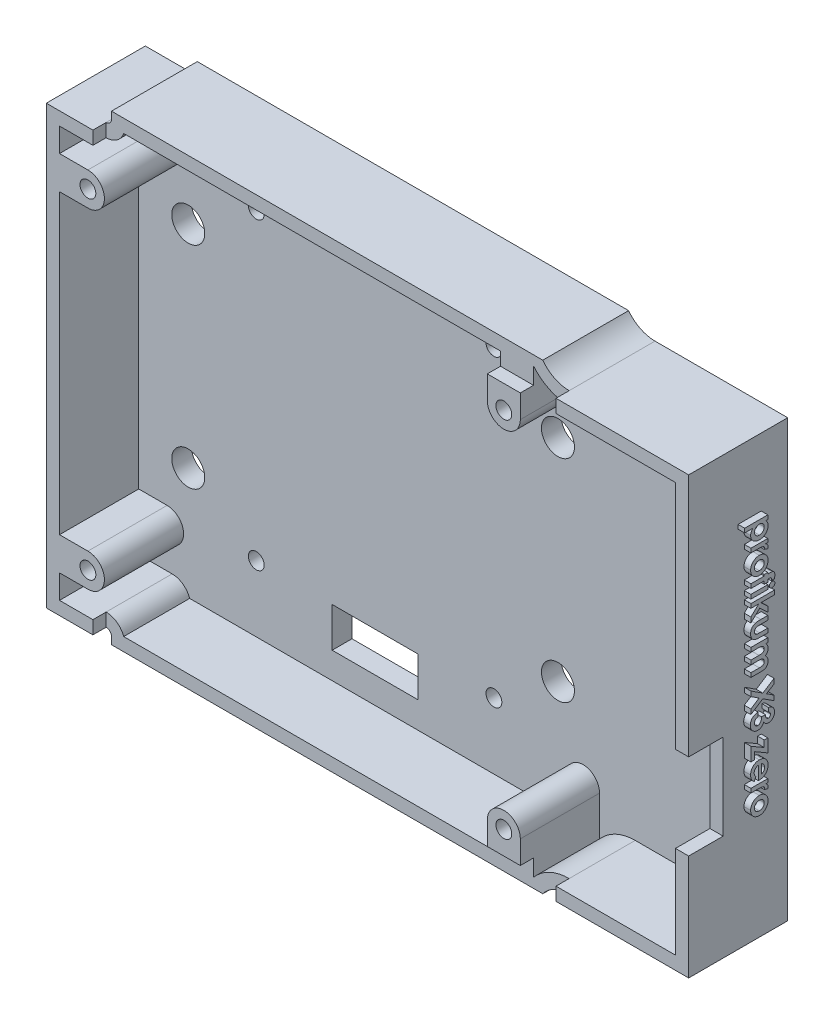
SolidWorks part; units mm, degrees
ref_plane "Ebene vorne" through (0, 0, 0) normal (0, 0, 1) x (1, 0, 0)
ref_plane "Ebene oben" through (0, 0, 0) normal (0, 1, 0) x (1, 0, 0)
ref_plane "Ebene rechts" through (0, 0, 0) normal (1, 0, 0) x (0, 0, -1)
sketch "Skizze1" plane through (0, 0, 0) normal (0, 0, 1) x (1, 0, 0)
  line L0 (-40.78, 38.7) -> (-40.78, 33.92)
  line L1 (-41.59, 33.11) -> (-48.65, 33.11)
  line L2 (-48.65, 33.11) -> (-48.65, -33.11)
  line L3 (-48.65, -33.11) -> (-41.59, -33.11)
  line L4 (-40.78, -33.92) -> (-40.78, -38.7)
  line L5 (-40.78, -38.7) -> (-39.35, -38.7)
  line L6 (-39.35, -38.7) -> (-39.35, 38.7)
  line L7 (-39.35, 38.7) -> (-40.78, 38.7)
  line L8 (48.65, 3) -> (45.65, 3)
  line L9 (45.65, 3) -> (45.65, -30)
  line L10 (45.65, -30) -> (34.2, -30)
  line L11 (34.2, -33) -> (48.65, -33)
  line L12 (48.65, -33) -> (48.65, 3)
  line L13 (45.65, 18) -> (48.65, 18)
  line L14 (48.65, 18) -> (48.65, 33)
  line L15 (48.65, 33) -> (34.2, 33)
  line L16 (34.2, 30) -> (45.65, 30)
  line L17 (45.65, 30) -> (45.65, 18)
  line L18 (34.2, 33) -> (28.5521, 33)
  line L19 (23.85, 36.3) -> (5.65, 36.3)
  line L20 (2.287, 35) -> (-20.522, 35)
  line L21 (-25.35, 38.7) -> (-27.35, 38.7)
  line L22 (-27.35, 38.7) -> (-27.35, -38.7)
  line L23 (-27.35, -38.7) -> (-25.35, -38.7)
  line L24 (-20.522, -35) -> (2.287, -35)
  line L25 (5.65, -36.3) -> (23.85, -36.3)
  line L26 (28.5521, -33) -> (34.2, -33)
  line L27 (34.2, -30) -> (23.85, -30)
  line L28 (23.85, -30) -> (23.85, -24)
  line L29 (23.85, -24) -> (17.45, -24)
  line L30 (17.45, -24) -> (17.45, -33.3)
  line L31 (17.45, -33.3) -> (9.3559, -33.3)
  line L32 (7.65, -33) -> (-24.35, -33)
  line L33 (-24.35, -33) -> (-24.35, 33)
  line L34 (-24.35, 33) -> (7.65, 33)
  line L35 (9.3559, 33.3) -> (17.45, 33.3)
  line L36 (17.45, 33.3) -> (17.45, 24)
  line L37 (17.45, 24) -> (23.85, 24)
  line L38 (23.85, 24) -> (23.85, 30)
  line L39 (23.85, 30) -> (34.2, 30)
  line L40 (-39.35, -38.7) -> (-27.35, -38.7)
  line L41 (-39.35, 38.7) -> (-27.35, 38.7)
  line L42 (48.65, 18) -> (48.65, 3)
  arc A0 (-41.59, 33.11) -> (-40.78, 33.92) centre (-41.59, 33.92) ccw
  arc A1 (-40.78, -33.92) -> (-41.59, -33.11) centre (-41.59, -33.92) ccw
  arc A2 (23.85, 36.3) -> (28.5521, 33) centre (28.5521, 38) ccw
  arc A3 (2.287, 35) -> (5.65, 36.3) centre (2.287, 40) ccw
  arc A4 (-25.35, 38.7) -> (-20.522, 35) centre (-20.522, 40) ccw
  arc A5 (-20.522, -35) -> (-25.35, -38.7) centre (-20.522, -40) ccw
  arc A6 (5.65, -36.3) -> (2.287, -35) centre (2.287, -40) ccw
  arc A7 (28.5521, -33) -> (23.85, -36.3) centre (28.5521, -38) ccw
  arc A8 (7.65, -33) -> (9.3559, -33.3) centre (9.3559, -28.3) ccw
  arc A9 (9.3559, 33.3) -> (7.65, 33) centre (9.3559, 28.3) ccw
extrude "Aufsatz-Linear austragen1" add sketch "Skizze1" along normal blind 15 contours A1 L4 L5 L6 L7 L0 A0 L1 L2 L3 | L41 L6 L40 L22 | A9 L35 L36 L37 L38 L39 L16 L17 L13 L14 L15 L18 A2 L19 A3 L20 A4 L21 L22 L23 A5 L24 A6 L25 A7 L26 L11 L12 L8 L9 L10 L27 L28 L29 L30 L31 A8 L32 L33 L34 | L35 A9 L34 L33 L32 A8 L31 L30 L29 L28 L27 L10 L9 L8 L42 L13 L17 L16 L39 L38 L37 L36 region at (-43.8991, 0, 0) region at (-33.35, 0, 0) region at (-26.35, 37.6153, 0) region at (10.0511, 0.1068, 0)
sketch "Skizze7" plane through (0, 0, 0) normal (0, 0, -1) x (-1, 0, 0)
  line L1 (17.35, -29) -> (4.35, -29)
  line L2 (17.35, -29) -> (17.35, -23)
  line L3 (17.35, -23) -> (4.35, -23)
  line L4 (4.35, -29) -> (4.35, -23)
  line L5 (17.35, 23) -> (4.35, 23)
  line L6 (17.35, 23) -> (17.35, 29)
  line L7 (17.35, 29) -> (4.35, 29)
  line L8 (4.35, 23) -> (4.35, 29)
extrude "Schnitt-Linear austragen6" cut sketch "Skizze7" against normal through all both
sketch "Skizze2" plane through (0, 0, 15) normal (0, 0, 1) x (1, 0, 0)
  line L56 (46.65, -31) -> (46.65, 31)
  line L57 (46.65, 31) -> (28.5521, 31)
  line L58 (22.6099, 34.3) -> (6.3502, 34.3)
  line L59 (2.287, 33) -> (-20.522, 33)
  line L60 (-26.6953, 36.7) -> (-38.78, 36.7)
  line L61 (-38.78, 36.7) -> (-38.78, 33.92)
  line L62 (-41.59, 31.11) -> (-46.65, 31.11)
  line L63 (-46.65, 31.11) -> (-46.65, -31.11)
  line L64 (-46.65, -31.11) -> (-41.59, -31.11)
  line L65 (-38.78, -33.92) -> (-38.78, -36.7)
  line L66 (-38.78, -36.7) -> (-26.6953, -36.7)
  line L67 (-20.522, -33) -> (2.287, -33)
  line L68 (6.3502, -34.3) -> (22.6099, -34.3)
  line L69 (28.5521, -31) -> (46.65, -31)
  line L70 (46.65, -31) -> (46.65, 31)
  line L71 (46.65, 31) -> (28.5521, 31)
  line L72 (22.6099, 34.3) -> (6.3502, 34.3)
  line L73 (2.287, 33) -> (-20.522, 33)
  line L74 (-26.6953, 36.7) -> (-38.78, 36.7)
  line L75 (-38.78, 36.7) -> (-38.78, 33.92)
  line L76 (-41.59, 31.11) -> (-46.65, 31.11)
  line L77 (-46.65, 31.11) -> (-46.65, -31.11)
  line L78 (-46.65, -31.11) -> (-41.59, -31.11)
  line L79 (-38.78, -33.92) -> (-38.78, -36.7)
  line L80 (-38.78, -36.7) -> (-26.6953, -36.7)
  line L81 (-20.522, -33) -> (2.287, -33)
  line L82 (6.3502, -34.3) -> (22.6099, -34.3)
  line L83 (28.5521, -31) -> (46.65, -31)
  arc A32 (22.6099, 34.3) -> (28.5521, 31) centre (28.5521, 38) ccw
  arc A33 (2.287, 33) -> (6.3502, 34.3) centre (2.287, 40) ccw
  arc A34 (-26.6953, 36.7) -> (-20.522, 33) centre (-20.522, 40) ccw
  arc A35 (-41.59, 31.11) -> (-38.78, 33.92) centre (-41.59, 33.92) ccw
  arc A36 (-38.78, -33.92) -> (-41.59, -31.11) centre (-41.59, -33.92) ccw
  arc A37 (-20.522, -33) -> (-26.6953, -36.7) centre (-20.522, -40) ccw
  arc A38 (6.3502, -34.3) -> (2.287, -33) centre (2.287, -40) ccw
  arc A39 (28.5521, -31) -> (22.6099, -34.3) centre (28.5521, -38) ccw
  arc A40 (22.6099, 34.3) -> (28.5521, 31) centre (28.5521, 38) ccw
  arc A41 (2.287, 33) -> (6.3502, 34.3) centre (2.287, 40) ccw
  arc A42 (-26.6953, 36.7) -> (-20.522, 33) centre (-20.522, 40) ccw
  arc A43 (-41.59, 31.11) -> (-38.78, 33.92) centre (-41.59, 33.92) ccw
  arc A44 (-38.78, -33.92) -> (-41.59, -31.11) centre (-41.59, -33.92) ccw
  arc A45 (-20.522, -33) -> (-26.6953, -36.7) centre (-20.522, -40) ccw
  arc A46 (6.3502, -34.3) -> (2.287, -33) centre (2.287, -40) ccw
  arc A47 (28.5521, -31) -> (22.6099, -34.3) centre (28.5521, -38) ccw
  dimension "D1" = 2
extrude "Schnitt-Linear austragen1" cut sketch "Skizze2" against normal blind 12
sketch "Skizze3" plane through (0, 0, 3) normal (0, 0, 1) x (1, 0, 0)
  line L0 (-48.65, 0) -> (48.65, 0) construction
  line L1 (-48.65, 0) -> (48.65, 0) construction
  line L2 (48.65, -33) -> (48.65, 33) construction
  line L3 (-48.65, 33.11) -> (-48.65, -33.11) construction
  circle A5 centre (-42.35, 25) radius 1.2
  circle A6 centre (20.65, 27.5) radius 1.2
  circle A7 centre (20.65, -27.5) radius 1.2
  circle A8 centre (-42.35, -25) radius 1.2
  dimension "D1" = 2.4
  dimension "D2" = 2.4
extrude "Schnitt-Linear austragen2" cut sketch "Skizze3" against normal blind 10
sketch "Skizze4" plane through (48.65, 0, 0) normal (1, 0, 0) x (0, 0, -1)
  line L0 (-15, -33) -> (-15, 33) construction
  line L1 (-15, -4) -> (-9.78, -4)
  line L2 (-15, -4) -> (-15, -17)
  line L3 (-15, -17) -> (-9.78, -17)
  line L4 (-9.78, -4) -> (-9.78, -17)
  line L5 (-15, -4) -> (-19.215, -4) construction
  point P9 (-12.39, -17)
  dimension "D1" = 5.22
  dimension "D2" = 13
extrude "Schnitt-Linear austragen3" cut sketch "Skizze4" against normal blind 5
sketch "Skizze5" plane through (0, 0, 0) normal (0, 0, -1) x (-1, 0, 0)
  circle A4 centre (-7.15, 23) radius 1.2
  circle A5 centre (28.85, 23) radius 1.2
  circle A6 centre (-7.15, -23) radius 1.2
  circle A7 centre (28.85, -23) radius 1.2
extrude "Schnitt-Linear austragen4" cut sketch "Skizze5" against normal through all both
sketch "Skizze6" plane through (0, 0, 0) normal (0, 0, -1) x (-1, 0, 0)
  line L0 (11.15, -17.75) -> (11.15, 17.75) construction
  line L1 (-21.35, -17.75) -> (43.65, -17.75) construction
  line L2 (43.65, 17.75) -> (-21.35, 17.75) construction
  line L3 (48.65, 0) -> (-26.35, 0) construction
  line L4 (48.65, 33.11) -> (48.65, -33.11) construction
  line L5 (-26.35, -10) -> (-26.35, 10) construction
  circle A0 centre (-16.85, -16) radius 2.5
  circle A1 centre (-16.85, 16) radius 2.5
  circle A2 centre (39.15, 16) radius 2.5
  circle A3 centre (39.15, -16) radius 2.5
  dimension "D1" = 5
  dimension "D2" = 28
  dimension "D3" = 16
extrude "Schnitt-Linear austragen5" cut sketch "Skizze6" against normal through all both
sketch "Skizze8" plane through (0, 0, 3) normal (0, 0, 1) x (1, 0, 0)
  line L0 (-48.65, 0) -> (48.65, 0) construction
  line L1 (-48.65, 33.11) -> (-48.65, -33.11) construction
  line L2 (48.65, -4) -> (48.65, 33) construction
  line L3 (0, 0) -> (0, 35) construction
  line L4 (2.287, 35) -> (-20.522, 35) construction
  circle A0 centre (-42.35, 25) radius 2.5
  circle A1 centre (-42.35, 25) radius 1.2
  circle A2 centre (-42.35, -25) radius 1.2
  circle A3 centre (-42.35, -25) radius 2.5
  circle A4 centre (20.65, 27.5) radius 2.5
  circle A5 centre (20.65, 27.5) radius 1.2
  circle A6 centre (20.65, -27.5) radius 1.2
  circle A7 centre (20.65, -27.5) radius 2.5
  dimension "D1" = 5
  dimension "D2" = 5
extrude "Aufsatz-Linear austragen2" add sketch "Skizze8" along normal up to surface (12 mm away) up to face at (-5.0444, -0.875, 15)
sketch "Skizze9" plane through (0, 0, 3) normal (0, 0, 1) x (1, 0, 0)
  line L0 (20.6578, 29.8022) -> (20.6578, 36.7352)
  line L1 (20.6578, 36.7352) -> (-46.65, 36.7352)
  line L2 (-46.65, 36.7352) -> (-46.65, 27.3022)
  line L3 (-46.65, 31.11) -> (-46.65, -31.11) construction
  line L4 (-46.65, 27.3022) -> (18.1578, 27.3022)
  line L5 (-48.65, 0) -> (46.65, 0) construction
  line L6 (-48.65, 33.11) -> (-48.65, -33.11) construction
  line L7 (46.65, -31) -> (46.65, 31) construction
  line L9 (18.15, 33) -> (18.15, 27.5)
  line L17 (-46.65, -27.3022) -> (18.1578, -27.3022)
  line L18 (-46.65, -36.7352) -> (-46.65, -27.3022)
  line L19 (20.6578, -36.7352) -> (-46.65, -36.7352)
  line L20 (20.6578, -29.8022) -> (20.6578, -36.7352)
  line L21 (-20.522, -33) -> (-38.9349, -33)
  line L22 (-20.522, -35) -> (-38.78, -35)
  line L23 (-38.78, -33.92) -> (-38.78, -36.7) construction
  line L24 (-38.78, -35) -> (-38.9349, -33)
  line L25 (-20.522, -33) -> (-20.522, -35)
  line L26 (-20.522, 33) -> (-20.522, 35)
  line L27 (-38.78, 35) -> (-38.9349, 33)
  line L28 (-20.522, 35) -> (-38.78, 35)
  line L29 (-20.522, 33) -> (-38.9349, 33)
  line L30 (2.287, 33) -> (18.15, 33)
  line L31 (2.287, 35) -> (24.5521, 35)
  line L32 (24.5521, 35) -> (24.5521, 34.3)
  line L33 (23.15, 34.3) -> (24.5521, 34.3)
  line L34 (2.287, 35) -> (2.287, 33)
  line L35 (2.287, -35) -> (2.287, -33)
  line L36 (23.15, -34.3) -> (24.5521, -34.3)
  line L37 (24.5521, -35) -> (24.5521, -34.3)
  line L38 (2.287, -35) -> (24.5521, -35)
  line L39 (2.287, -33) -> (18.15, -33)
  line L40 (23.15, -27.5) -> (23.15, -34.3)
  line L41 (18.15, -27.5) -> (18.15, -33)
  line L42 (23.15, 34.3) -> (23.15, 27.5)
  circle A0 centre (20.65, 27.5) radius 2.5 construction
  circle A1 centre (20.65, 27.5) radius 2.5 construction
  arc A2 (20.6578, 29.8022) -> (18.1578, 27.3022) centre (18.1578, 29.8022) cw
  circle A3 centre (18.1578, 29.8022) radius 1.2
  arc A6 (18.15, 27.5) -> (23.15, 27.5) centre (20.65, 27.5) ccw
  circle A11 centre (18.1578, -29.8022) radius 1.2
  arc A12 (20.6578, -29.8022) -> (18.1578, -27.3022) centre (18.1578, -29.8022) ccw
  arc A13 (-38.78, -33.92) -> (-41.59, -31.11) centre (-41.59, -33.92) ccw construction
  arc A14 (23.85, 36.3) -> (28.5521, 33) centre (28.5521, 38) ccw construction
  circle A15 centre (20.65, -27.5) radius 1.2
  arc A16 (23.15, -27.5) -> (18.15, -27.5) centre (20.65, -27.5) ccw
  circle M1 centre (20.65, 27.5) radius 2.5
  arc M22 (28.5521, 31) -> (22.6099, 34.3) centre (28.5521, 38) cw
  line M23 (22.6099, 34.3) -> (6.3502, 34.3)
  arc M24 (6.3502, 34.3) -> (2.287, 33) centre (2.287, 40) cw
  arc M38 (2.287, -33) -> (6.3502, -34.3) centre (2.287, -40) cw
  line M39 (6.3502, -34.3) -> (22.6099, -34.3)
  arc M40 (22.6099, -34.3) -> (28.5521, -31) centre (28.5521, -38) cw
  circle M42 centre (20.65, -27.5) radius 2.5
  dimension "D1" = 2.5
extrude "Aufsatz-Linear austragen3" add sketch "Skizze9" along normal up to surface (12 mm away) contours L40 L20 M42 M39 M40 | A11 L41 M42 | L42 L0 M22 M23 M1 | A3 L0 L30 L9 M1 M23 M24 | L9 A3 M1 | A3 L9 M1 | A11 L41 L39 L20 M42 M38 M39 | L41 A11 M42 region at (14.4987, 33.1222, 3) region at (21.9627, 31.8094, 3) region at (18.6267, 29.9018, 3) region at (18.2291, 28.3365, 3) region at (21.9627, -31.8094, 3) region at (18.2291, -28.3365, 3) region at (14.4987, -33.1222, 3) region at (18.6267, -29.9018, 3) up to face at (-5.0444, -0.875, 15)
sketch "Skizze10" plane through (0, 0, 15) normal (0, 0, 1) x (1, 0, 0)
  line L0 (-40.78, 38.7) -> (-40.78, 33.92) construction
  line L1 (-40.78, 35) -> (36.193, 35)
  line L2 (-40.78, 35) -> (-40.78, 40.1609)
  line L3 (-40.78, 40.1609) -> (36.193, 40.1609)
  line L4 (36.193, 35) -> (36.193, 40.1609)
  line L5 (-48.65, 0) -> (46.65, 0) construction
  line L6 (-48.65, 33.11) -> (-48.65, -33.11) construction
  line L7 (46.65, -31) -> (46.65, 31) construction
  line L8 (36.193, -35) -> (36.193, -40.1609)
  line L9 (-40.78, -40.1609) -> (36.193, -40.1609)
  line L10 (-40.78, -35) -> (-40.78, -40.1609)
  line L11 (-40.78, -35) -> (36.193, -35)
extrude "Schnitt-Linear austragen7" cut sketch "Skizze10" against normal through all both and the other way through all
sketch "Skizze11" plane through (0, 0, 15) normal (0, 0, 1) x (1, 0, 0)
  line L19 (-48.65, 0) -> (0, 0) construction
  line L20 (-48.65, 33.11) -> (-48.65, -33.11) construction
  line L33 (-41.59, 31.11) -> (-41.59, 35)
  line L34 (-41.59, 35) -> (28.5521, 35)
  line L35 (28.5521, 35) -> (28.5521, 31)
  line L36 (28.5521, 31) -> (18.15, 31)
  line L38 (18.15, 31) -> (18.15, 33)
  line L39 (18.15, 33) -> (-38.9349, 33)
  line L40 (-38.9349, 33) -> (-38.9349, 31.11)
  line L41 (-38.9349, 31.11) -> (-41.59, 31.11)
  line L42 (-38.9349, -33) -> (-38.9349, -31.11)
  line L43 (18.15, -33) -> (-38.9349, -33)
  line L44 (18.15, -31) -> (18.15, -33)
  line L45 (28.5521, -31) -> (18.15, -31)
  line L46 (28.5521, -35) -> (28.5521, -31)
  line L47 (-41.59, -35) -> (28.5521, -35)
  line L48 (-41.59, -31.11) -> (-41.59, -35)
  line L49 (-38.9349, -31.11) -> (-41.59, -31.11)
extrude "Schnitt-Linear austragen8" cut sketch "Skizze11" against normal blind 2
sketch "Skizze12" plane through (0, 0, 3) normal (0, 0, 1) x (1, 0, 0)
  line L0 (-56.6131, 0) -> (54.1226, 0) construction
  line L1 (-20.522, -35) -> (-20.522, -33)
  line L2 (-40.78, 35) -> (-20.522, 35)
  line L3 (-40.78, 35) -> (-40.78, 33)
  line L4 (-40.78, 33) -> (-20.522, 33)
  line L5 (-20.522, 35) -> (-20.522, 33)
  line L6 (-40.78, -33) -> (-20.522, -33)
  line L7 (-40.78, -35) -> (-40.78, -33)
  line L8 (-40.78, -35) -> (-20.522, -35)
extrude "Aufsatz-Linear austragen4" add sketch "Skizze12" along normal up to surface (10 mm away) up to face at (13.0662, 32.6656, 13)
sketch "Skizze13" plane through (0, 0, 3) normal (0, 0, 1) x (1, 0, 0)
  line L0 (-42.35, 27.5) -> (-46.65, 27.5)
  line L1 (-46.65, 31.11) -> (-46.65, -31.11) construction
  line L2 (-42.35, 22.5) -> (-46.65, 22.5)
  line L3 (-46.65, 22.5) -> (-46.65, 27.5)
  line L4 (-70.2115, 0) -> (90.3096, 0) construction
  line L5 (-46.65, -22.5) -> (-46.65, -27.5)
  line L6 (-42.35, -22.5) -> (-46.65, -22.5)
  line L7 (-42.35, -27.5) -> (-46.65, -27.5)
  circle A0 centre (-42.35, 25) radius 2.5 construction
  circle A1 centre (-42.35, 25) radius 2.5 construction
  arc A2 (-42.35, 27.5) -> (-42.35, 22.5) centre (-42.35, 25) ccw
  arc A3 (-42.35, -27.5) -> (-42.35, -22.5) centre (-42.35, -25) cw
extrude "Aufsatz-Linear austragen5" add sketch "Skizze13" along normal up to surface (12 mm away) up to face at (-41.15, 25, 15)
sketch "Skizze17" plane through (48.65, 0, 0) normal (1, 0, 0) x (0, 0, -1)
  line L0 (-4.0129, 22.1349) -> (-4.3011, 22.1349)
  line L1 (-6.2818, 22.1349) -> (-7.5129, 22.1349)
  line L2 (-7.5129, 22.1349) -> (-7.5129, 22.7631)
  line L3 (-7.5129, 22.7631) -> (-4.0129, 22.7631)
  line L4 (-4.0129, 22.7631) -> (-4.0129, 22.1349)
  line L5 (-4.0129, 19.6669) -> (-4.0129, 19.1284)
  line L6 (-4.0129, 19.1284) -> (-4.3277, 19.1284)
  line L7 (-4.0312, 18.3208) -> (-4.5633, 18.5157)
  line L8 (-5.4103, 19.0408) -> (-5.5351, 19.0387)
  line L9 (-5.5351, 19.0387) -> (-6.5706, 19.0387)
  line L10 (-6.5706, 19.0387) -> (-6.5706, 19.6669)
  line L11 (-6.5706, 19.6669) -> (-4.0129, 19.6669)
  line L12 (-4.0129, 15.2246) -> (-4.0129, 15.0002)
  line L13 (-3.0279, 13.8784) -> (-3.5165, 13.8784)
  line L14 (-3.6771, 14.3272) -> (-4.0129, 14.3293)
  line L15 (-4.0129, 14.3293) -> (-4.0129, 13.9233)
  line L16 (-4.0129, 13.9233) -> (-4.5514, 13.9233)
  line L17 (-4.5514, 13.9233) -> (-4.5514, 14.372)
  line L18 (-4.5514, 14.372) -> (-6.5706, 14.372)
  line L19 (-6.5706, 14.372) -> (-6.5706, 15.0002)
  line L20 (-6.5706, 15.0002) -> (-4.5514, 15.0002)
  line L21 (-4.5514, 15.0002) -> (-4.5514, 15.2246)
  line L22 (-4.5514, 15.2246) -> (-4.0129, 15.2246)
  line L23 (-4.0129, 13.6092) -> (-4.0129, 12.981)
  line L24 (-4.0129, 12.981) -> (-6.5706, 12.981)
  line L25 (-6.5706, 12.981) -> (-6.5706, 13.6092)
  line L26 (-6.5706, 13.6092) -> (-4.0129, 13.6092)
  line L27 (-2.9809, 12.3977) -> (-2.9809, 11.7695)
  line L28 (-2.9809, 11.7695) -> (-5.0744, 11.7695)
  line L29 (-5.0744, 11.7695) -> (-4.0129, 10.7921)
  line L30 (-4.0129, 10.7921) -> (-4.0129, 10.016)
  line L31 (-4.0129, 10.016) -> (-5.2322, 11.1385)
  line L32 (-5.2322, 11.1385) -> (-6.5706, 9.8554)
  line L33 (-6.5706, 9.8554) -> (-6.5706, 10.6463)
  line L34 (-6.5706, 10.6463) -> (-5.399, 11.7695)
  line L35 (-5.399, 11.7695) -> (-6.5706, 11.7695)
  line L36 (-6.5706, 11.7695) -> (-6.5706, 12.3977)
  line L37 (-6.5706, 12.3977) -> (-2.9809, 12.3977)
  line L38 (-4.0129, 9.5708) -> (-4.0129, 8.9425)
  line L39 (-4.0129, 8.9425) -> (-5.2406, 8.9425)
  line L40 (-5.2616, 7.9105) -> (-4.0129, 7.9105)
  line L41 (-4.0129, 7.9105) -> (-4.0129, 7.2823)
  line L42 (-4.0129, 7.2823) -> (-5.0877, 7.2823)
  line L43 (-5.0695, 9.5708) -> (-4.0129, 9.5708)
  line L44 (-4.0129, 6.6541) -> (-4.0129, 6.0259)
  line L45 (-4.0129, 6.0259) -> (-4.3186, 6.0259)
  line L46 (-5.0828, 2.7054) -> (-6.5706, 2.7054)
  line L47 (-6.5706, 2.7054) -> (-6.5706, 3.3336)
  line L48 (-6.5706, 3.3336) -> (-5.2862, 3.3336)
  line L49 (-5.4285, 4.3656) -> (-6.5706, 4.3656)
  line L50 (-6.5706, 4.3656) -> (-6.5706, 4.9938)
  line L51 (-6.5706, 4.9938) -> (-5.3444, 4.9938)
  line L52 (-5.4446, 6.0259) -> (-6.5706, 6.0259)
  line L53 (-6.5706, 6.0259) -> (-6.5706, 6.6541)
  line L54 (-6.5706, 6.6541) -> (-4.0129, 6.6541)
  line L55 (-3.0706, 0.8551) -> (-3.0706, 0.1147)
  line L56 (-3.0706, 0.1147) -> (-4.1945, -0.6165)
  line L57 (-4.1945, -0.6165) -> (-3.0706, -1.3492)
  line L58 (-3.0706, -1.3492) -> (-3.0706, -2.0903)
  line L59 (-3.0706, -2.0903) -> (-4.7631, -0.9867)
  line L60 (-4.7631, -0.9867) -> (-6.5706, -2.1632)
  line L61 (-6.5706, -2.1632) -> (-6.5706, -1.4228)
  line L62 (-6.5706, -1.4228) -> (-5.331, -0.6165)
  line L63 (-5.331, -0.6165) -> (-6.5706, 0.1918)
  line L64 (-6.5706, 0.1918) -> (-6.5706, 0.9329)
  line L65 (-6.5706, 0.9329) -> (-4.7624, -0.2464)
  line L66 (-4.7624, -0.2464) -> (-3.0706, 0.8551)
  line L67 (-3.9232, -3.1728) -> (-3.9232, -2.5446)
  line L68 (-5.4937, -2.3651) -> (-5.4937, -2.9933)
  line L69 (-4.9552, -3.2626) -> (-4.3719, -3.2626)
  line L70 (-4.0129, -6.4933) -> (-4.0129, -8.4677)
  line L71 (-4.0129, -8.4677) -> (-6.0322, -7.2912)
  line L72 (-6.0322, -7.2912) -> (-6.0322, -8.378)
  line L73 (-6.0322, -8.378) -> (-6.5706, -8.378)
  line L74 (-6.5706, -8.378) -> (-6.5706, -6.3139)
  line L75 (-6.5706, -6.3139) -> (-4.5514, -7.4903)
  line L76 (-4.5514, -7.4903) -> (-4.5514, -6.4933)
  line L77 (-4.5514, -6.4933) -> (-4.0129, -6.4933)
  line L78 (-5.4488, -11.3823) -> (-5.4488, -9.3651)
  line L79 (-5.8113, -10.679) -> (-6.0616, -11.2049)
  line L80 (-5.3303, -11.3844) -> (-5.4488, -11.3823)
  line L81 (-4.9552, -9.41) -> (-4.9552, -10.7562)
  line L82 (-4.0129, -11.8331) -> (-4.0129, -12.3716)
  line L83 (-4.0129, -12.3716) -> (-4.3277, -12.3716)
  line L84 (-4.0312, -13.1792) -> (-4.5633, -12.9843)
  line L85 (-5.4103, -12.4592) -> (-5.5351, -12.4613)
  line L86 (-5.5351, -12.4613) -> (-6.5706, -12.4613)
  line L87 (-6.5706, -12.4613) -> (-6.5706, -11.8331)
  line L88 (-6.5706, -11.8331) -> (-4.0129, -11.8331)
  spline S0 degree 3 poles (-4.3011, 22.1349) (-4.2469, 22.0791) (-4.1746, 21.9887) (-4.0965, 21.8582) (-4.0499, 21.7575) (-4.0133, 21.6538) (-3.9784, 21.5093) (-3.9672, 21.3976) (-3.9681, 21.3223) knots 0 0 0 0 0.258836 0.383778 0.505657 0.627755 0.749517 1 1 1 1
  spline S1 degree 3 poles (-3.9681, 21.3223) (-3.9678, 21.2412) (-3.9787, 21.1205) (-4.0185, 20.9661) (-4.0594, 20.8562) (-4.1126, 20.7515) (-4.1763, 20.6507) (-4.253, 20.5556) (-4.34, 20.4661) (-4.4354, 20.3833) (-4.539, 20.3114) (-4.6496, 20.2514) (-4.7658, 20.2006) (-4.8896, 20.1635) (-5.0658, 20.1245) (-5.2037, 20.1165) (-5.2967, 20.1156) knots 0 0 0 0 0.12138 0.180256 0.238142 0.296489 0.355776 0.416247 0.479076 0.54232 0.604902 0.667516 0.730346 0.794405 0.860608 1 1 1 1
  spline S2 degree 3 poles (-5.2967, 20.1156) (-5.387, 20.1159) (-5.5208, 20.1254) (-5.6924, 20.1645) (-5.8133, 20.2048) (-5.9287, 20.2561) (-6.0384, 20.3187) (-6.1423, 20.3929) (-6.2387, 20.4778) (-6.3261, 20.5705) (-6.4044, 20.6672) (-6.4686, 20.7696) (-6.5229, 20.8753) (-6.5643, 20.9859) (-6.6037, 21.1404) (-6.6166, 21.2604) (-6.6155, 21.3412) knots 0 0 0 0 0.135343 0.199959 0.263049 0.325881 0.388744 0.451973 0.516706 0.580831 0.6426 0.702706 0.761562 0.820266 0.879182 1 1 1 1
  spline S3 degree 3 poles (-6.6155, 21.3412) (-6.6159, 21.4132) (-6.6056, 21.5198) (-6.574, 21.6576) (-6.5391, 21.7563) (-6.4927, 21.8527) (-6.4133, 21.9843) (-6.3371, 22.0756) (-6.2818, 22.1349) knots 0 0 0 0 0.243991 0.362118 0.479017 0.598573 0.724533 1 1 1 1
  spline S4 degree 3 poles (-4.5514, 21.4583) (-4.5524, 21.5081) (-4.5566, 21.5823) (-4.5791, 21.6767) (-4.6006, 21.7434) (-4.6296, 21.8065) (-4.6647, 21.8665) (-4.7066, 21.9228) (-4.7536, 21.9758) (-4.8065, 22.0234) (-4.8631, 22.0657) (-4.9239, 22.1008) (-4.9884, 22.1301) (-5.0572, 22.1522) (-5.1557, 22.1745) (-5.2328, 22.1788) (-5.2848, 22.1797) knots 0 0 0 0 0.129944 0.191681 0.251804 0.311878 0.37178 0.43216 0.494106 0.5556 0.61683 0.677256 0.737884 0.800505 0.864611 1 1 1 1
  spline S5 degree 3 poles (-5.2848, 22.1797) (-5.3379, 22.1788) (-5.4166, 22.1745) (-5.5171, 22.1523) (-5.587, 22.1298) (-5.6531, 22.101) (-5.7155, 22.066) (-5.7728, 22.0232) (-5.8271, 21.9761) (-5.8747, 21.9228) (-5.9175, 21.8667) (-5.9527, 21.8065) (-5.9812, 21.7431) (-6.0049, 21.677) (-6.0267, 21.5822) (-6.0313, 21.5082) (-6.0322, 21.4583) knots 0 0 0 0 0.137034 0.201676 0.264245 0.325918 0.386785 0.447889 0.509667 0.571399 0.631536 0.690841 0.750317 0.810229 0.871351 1 1 1 1
  spline S6 degree 3 poles (-6.0322, 21.4583) (-6.0318, 21.4097) (-6.0259, 21.3378) (-6.0039, 21.2455) (-5.9808, 21.1804) (-5.9508, 21.1182) (-5.9156, 21.0583) (-5.8717, 21.0028) (-5.8234, 20.9495) (-5.7689, 20.9019) (-5.7111, 20.8591) (-5.6493, 20.8232) (-5.5834, 20.7947) (-5.5146, 20.7711) (-5.4159, 20.7493) (-5.3389, 20.7448) (-5.2869, 20.7438) knots 0 0 0 0 0.1264 0.186368 0.246314 0.305548 0.365765 0.426397 0.489164 0.552425 0.614149 0.675935 0.737677 0.800494 0.864605 1 1 1 1
  spline S7 degree 3 poles (-5.2869, 20.7438) (-5.2354, 20.7449) (-5.1589, 20.7489) (-5.0615, 20.7716) (-4.993, 20.7927) (-4.9287, 20.8222) (-4.8678, 20.857) (-4.8102, 20.8981) (-4.7574, 20.9457) (-4.7094, 20.9979) (-4.6669, 21.0536) (-4.6308, 21.1126) (-4.6023, 21.1757) (-4.5788, 21.2415) (-4.5568, 21.3355) (-4.5522, 21.4088) (-4.5514, 21.4583) knots 0 0 0 0 0.134802 0.198611 0.260756 0.321667 0.382903 0.4437 0.505935 0.568128 0.628667 0.688638 0.748437 0.809234 0.870665 1 1 1 1
  spline S8 degree 3 poles (-4.3277, 19.1284) (-4.2726, 19.1) (-4.194, 19.0516) (-4.1099, 18.9659) (-4.0583, 18.8972) (-4.0182, 18.8224) (-3.9797, 18.7168) (-3.9674, 18.6328) (-3.9681, 18.5767) knots 0 0 0 0 0.268422 0.393205 0.51643 0.637793 0.758061 1 1 1 1
  spline S9 degree 3 poles (-3.9681, 18.5767) (-3.969, 18.5348) (-3.9786, 18.4459) (-4.0122, 18.3631) (-4.0312, 18.3208) knots 0 0 0 0 0.474168 1 1 1 1
  spline S10 degree 3 poles (-4.5633, 18.5157) (-4.5476, 18.5483) (-4.5195, 18.606) (-4.5068, 18.6691) (-4.5065, 18.6966) knots 0 0 0 0 0.570645 1 1 1 1
  spline S11 degree 3 poles (-4.5065, 18.6966) (-4.5065, 18.72) (-4.5117, 18.7559) (-4.5321, 18.7995) (-4.5515, 18.8318) (-4.5785, 18.8611) (-4.6098, 18.8904) (-4.6484, 18.9162) (-4.6914, 18.9434) (-4.744, 18.9665) (-4.8068, 18.9864) (-4.8805, 19.0041) (-4.9656, 19.0163) (-5.0611, 19.0281) (-5.2105, 19.038) (-5.3282, 19.0414) (-5.4103, 19.0408) knots 0 0 0 0 0.066912 0.101141 0.136381 0.173598 0.214076 0.25798 0.305417 0.358685 0.420924 0.492691 0.574131 0.665182 0.766513 1 1 1 1
  spline S12 degree 3 poles (-3.9681, 16.7881) (-3.9681, 16.7293) (-3.9734, 16.6413) (-3.9926, 16.5259) (-4.011, 16.4409) (-4.0368, 16.3577) (-4.0677, 16.2758) (-4.1032, 16.1947) (-4.1455, 16.1162) (-4.1913, 16.0398) (-4.2419, 15.9674) (-4.2968, 15.8995) (-4.3548, 15.835) (-4.4183, 15.7768) (-4.4844, 15.7212) (-4.5553, 15.6711) (-4.6294, 15.6248) (-4.7062, 15.5836) (-4.7853, 15.5478) (-4.8654, 15.5167) (-4.9476, 15.4924) (-5.0308, 15.4723) (-5.1449, 15.4551) (-5.2315, 15.4486) (-5.2897, 15.449) knots 0 0 0 0 0.084364 0.126142 0.167706 0.209066 0.250973 0.293148 0.336041 0.378761 0.420893 0.462622 0.503914 0.545188 0.586138 0.627722 0.669585 0.711432 0.752691 0.793971 0.834592 0.875577 0.91664 1 1 1 1
  spline S13 degree 3 poles (-5.2897, 15.449) (-5.3482, 15.449) (-5.4358, 15.4543) (-5.5505, 15.4735) (-5.635, 15.4919) (-5.7175, 15.5176) (-5.799, 15.5477) (-5.8785, 15.5845) (-5.9568, 15.6253) (-6.0317, 15.6719) (-6.1034, 15.7218) (-6.1699, 15.7772) (-6.2334, 15.835) (-6.2917, 15.8978) (-6.3458, 15.9648) (-6.3962, 16.0353) (-6.4419, 16.1098) (-6.4821, 16.1874) (-6.5183, 16.2667) (-6.5484, 16.3483) (-6.573, 16.4319) (-6.592, 16.5176) (-6.6095, 16.6354) (-6.6158, 16.725) (-6.6155, 16.7853) knots 0 0 0 0 0.083839 0.125192 0.166335 0.207602 0.24867 0.290582 0.332926 0.374978 0.416741 0.457857 0.498809 0.539516 0.58042 0.62191 0.663502 0.705394 0.746864 0.788245 0.829736 0.871532 0.913825 1 1 1 1
  spline S14 degree 3 poles (-6.6155, 16.7853) (-6.6146, 16.8728) (-6.6047, 17.0032) (-6.5636, 17.1704) (-6.5214, 17.2895) (-6.4672, 17.4039) (-6.4002, 17.5126) (-6.3216, 17.6166) (-6.2321, 17.7142) (-6.1339, 17.8036) (-6.0291, 17.8817) (-5.9193, 17.948) (-5.8042, 18.0025) (-5.6839, 18.0445) (-5.5145, 18.0857) (-5.3826, 18.0955) (-5.2939, 18.0964) knots 0 0 0 0 0.126884 0.188201 0.248894 0.309599 0.371125 0.433466 0.498143 0.562593 0.625474 0.687114 0.748125 0.809457 0.871431 1 1 1 1
  spline S15 degree 3 poles (-5.2939, 18.0964) (-5.1991, 18.0962) (-5.0589, 18.0835) (-4.8791, 18.038) (-4.7524, 17.99) (-4.6319, 17.9286) (-4.4772, 17.8276) (-4.3746, 17.7317) (-4.3109, 17.6624) knots 0 0 0 0 0.256474 0.379237 0.500978 0.622367 0.744855 1 1 1 1
  spline S16 degree 3 poles (-4.3109, 17.6624) (-4.2548, 17.6014) (-4.1808, 17.503) (-4.1006, 17.3622) (-4.0516, 17.2545) (-4.0148, 17.1427) (-3.9785, 16.988) (-3.9684, 16.8684) (-3.9681, 16.7881) knots 0 0 0 0 0.258464 0.38258 0.504991 0.627227 0.749297 1 1 1 1
  spline S17 degree 3 poles (-4.5514, 16.7741) (-4.5527, 16.8218) (-4.5561, 16.8932) (-4.5798, 16.9834) (-4.6021, 17.0476) (-4.6319, 17.1081) (-4.6667, 17.1667) (-4.7103, 17.2202) (-4.7581, 17.2713) (-4.8112, 17.3177) (-4.8691, 17.3573) (-4.9295, 17.3926) (-4.9946, 17.4194) (-5.0627, 17.4415) (-5.1606, 17.4621) (-5.2365, 17.4691) (-5.2883, 17.4682) knots 0 0 0 0 0.126803 0.187423 0.246518 0.306285 0.365703 0.426477 0.488622 0.550895 0.612679 0.673914 0.735734 0.798735 0.86329 1 1 1 1
  spline S18 degree 3 poles (-5.2883, 17.4682) (-5.3413, 17.4684) (-5.4193, 17.4632) (-5.5194, 17.4422) (-5.5888, 17.4204) (-5.6546, 17.3929) (-5.7166, 17.3593) (-5.7742, 17.319) (-5.8274, 17.2734) (-5.8757, 17.2235) (-5.9172, 17.1687) (-5.9533, 17.1115) (-5.9822, 17.0505) (-6.0045, 16.9865) (-6.0269, 16.8955) (-6.0312, 16.8242) (-6.0322, 16.7762) knots 0 0 0 0 0.139456 0.204809 0.268587 0.330587 0.392213 0.45361 0.515092 0.576402 0.636039 0.695407 0.753981 0.813285 0.873377 1 1 1 1
  spline S19 degree 3 poles (-6.0322, 16.7762) (-6.032, 16.728) (-6.0257, 16.6567) (-6.004, 16.5653) (-5.9815, 16.5008) (-5.9519, 16.4398) (-5.9157, 16.3819) (-5.8736, 16.3268) (-5.8244, 16.2761) (-5.771, 16.2293) (-5.7131, 16.1882) (-5.6512, 16.1539) (-5.5856, 16.1257) (-5.5166, 16.1039) (-5.4176, 16.0832) (-5.3407, 16.0763) (-5.2883, 16.0772) knots 0 0 0 0 0.126397 0.186939 0.246099 0.305348 0.364572 0.424924 0.486952 0.54955 0.611149 0.672922 0.73501 0.798049 0.862643 1 1 1 1
  spline S20 degree 3 poles (-5.2883, 16.0772) (-5.236, 16.0769) (-5.1589, 16.0823) (-5.0602, 16.1031) (-4.9918, 16.1251) (-4.9268, 16.1524) (-4.8656, 16.1861) (-4.8084, 16.2265) (-4.7556, 16.2724) (-4.7079, 16.3231) (-4.6654, 16.3768) (-4.6303, 16.4349) (-4.6013, 16.4962) (-4.579, 16.5609) (-4.5566, 16.6531) (-4.5524, 16.7254) (-4.5514, 16.7741) knots 0 0 0 0 0.13784 0.202698 0.265406 0.326938 0.388125 0.449117 0.511101 0.572086 0.632197 0.691339 0.750564 0.810546 0.871335 1 1 1 1
  spline S21 degree 3 poles (-4.0129, 15.0002) (-3.936, 15.0004) (-3.8271, 14.9986) (-3.6906, 14.997) (-3.6079, 14.995) (-3.5385, 14.9921) (-3.4723, 14.9888) (-3.4292, 14.9863) (-3.4051, 14.9827) knots 0 0 0 0 0.379195 0.537106 0.673146 0.787338 0.879654 1 1 1 1
  spline S22 degree 3 poles (-3.4051, 14.9827) (-3.3379, 14.9739) (-3.2388, 14.9467) (-3.1284, 14.8705) (-3.0708, 14.8112) (-3.0315, 14.7561) (-3.0059, 14.71) (-2.9839, 14.6598) (-2.9666, 14.6054) (-2.9525, 14.5473) (-2.9391, 14.4618) (-2.9365, 14.3952) (-2.936, 14.3496) knots 0 0 0 0 0.233471 0.344313 0.457241 0.515357 0.576073 0.63824 0.703204 0.771713 0.843217 1 1 1 1
  spline S23 degree 3 poles (-2.936, 14.3496) (-2.9358, 14.2749) (-2.955, 14.1147) (-2.9999, 13.9599) (-3.0279, 13.8784) knots 0 0 0 0 0.464087 1 1 1 1
  spline S24 degree 3 poles (-3.5165, 13.8784) (-3.5043, 13.9219) (-3.4838, 14.0002) (-3.475, 14.0806) (-3.4745, 14.1161) knots 0 0 0 0 0.560116 1 1 1 1
  spline S25 degree 3 poles (-3.4745, 14.1161) (-3.4744, 14.1502) (-3.479, 14.2118) (-3.5051, 14.2682) (-3.5235, 14.2879) knots 0 0 0 0 0.562152 1 1 1 1
  spline S26 degree 3 poles (-3.5235, 14.2879) (-3.5395, 14.3027) (-3.5898, 14.3257) (-3.645, 14.3255) (-3.6771, 14.3272) knots 0 0 0 0 0.39829 1 1 1 1
  spline S27 degree 3 poles (-2.936, 13.2965) (-2.9351, 13.2434) (-2.9516, 13.1637) (-3.0053, 13.0702) (-3.06, 13.0084) (-3.1254, 12.957) (-3.224, 12.9039) (-3.3088, 12.8923) (-3.3644, 12.8913) knots 0 0 0 0 0.242963 0.363855 0.490606 0.61874 0.7433 1 1 1 1
  spline S28 degree 3 poles (-3.3644, 12.8913) (-3.4196, 12.8917) (-3.5028, 12.9049) (-3.6014, 12.956) (-3.6658, 13.0077) (-3.7196, 13.0689) (-3.7742, 13.1602) (-3.7885, 13.2395) (-3.7886, 13.2916) knots 0 0 0 0 0.256469 0.381955 0.510704 0.637377 0.757775 1 1 1 1
  spline S29 degree 3 poles (-3.7886, 13.2916) (-3.7895, 13.3453) (-3.7728, 13.4254) (-3.7195, 13.5202) (-3.6637, 13.5817) (-3.5978, 13.6336) (-3.4968, 13.6846) (-3.412, 13.6991) (-3.3553, 13.699) knots 0 0 0 0 0.242759 0.363443 0.489711 0.617482 0.74228 1 1 1 1
  spline S30 degree 3 poles (-3.3553, 13.699) (-3.3007, 13.6981) (-3.218, 13.6858) (-3.1212, 13.6339) (-3.057, 13.583) (-3.0033, 13.5217) (-2.9512, 13.4283) (-2.9356, 13.3493) (-2.936, 13.2965) knots 0 0 0 0 0.255027 0.378937 0.506523 0.634371 0.754976 1 1 1 1
  spline S31 degree 3 poles (-5.2406, 8.9425) (-5.2958, 8.9429) (-5.3751, 8.9411) (-5.4762, 8.9352) (-5.542, 8.93) (-5.6009, 8.9222) (-5.6529, 8.9132) (-5.6982, 8.903) (-5.7488, 8.8865) (-5.8041, 8.8605) (-5.8629, 8.8214) (-5.9137, 8.774) (-5.957, 8.7189) (-5.9911, 8.6556) (-6.0231, 8.5585) (-6.0327, 8.4802) (-6.0322, 8.4265) knots 0 0 0 0 0.152021 0.21846 0.279211 0.333765 0.382147 0.424476 0.461742 0.528577 0.592159 0.655492 0.719257 0.784372 0.852388 1 1 1 1
  spline S32 degree 3 poles (-6.0322, 8.4265) (-6.0317, 8.3729) (-6.0245, 8.2938) (-5.9912, 8.1966) (-5.9586, 8.1319) (-5.9148, 8.0752) (-5.8441, 8.008) (-5.7784, 7.9722) (-5.7321, 7.954) knots 0 0 0 0 0.269396 0.393097 0.513048 0.63087 0.750168 1 1 1 1
  spline S33 degree 3 poles (-5.7321, 7.954) (-5.7094, 7.9445) (-5.6698, 7.9362) (-5.6119, 7.9266) (-5.5569, 7.9202) (-5.4942, 7.9167) (-5.3949, 7.9113) (-5.3165, 7.9107) (-5.2616, 7.9105) knots 0 0 0 0 0.154778 0.255145 0.371211 0.504546 0.652553 1 1 1 1
  spline S34 degree 3 poles (-5.0877, 7.2823) (-5.1899, 7.2815) (-5.3366, 7.2852) (-5.523, 7.2969) (-5.6434, 7.3074) (-5.7508, 7.3228) (-5.8689, 7.3461) (-5.95, 7.3695) (-5.9978, 7.3903) knots 0 0 0 0 0.332669 0.477542 0.608237 0.725864 0.83063 1 1 1 1
  spline S35 degree 3 poles (-5.9978, 7.3903) (-6.0461, 7.4118) (-6.1155, 7.4483) (-6.2024, 7.5049) (-6.2617, 7.5519) (-6.3166, 7.6029) (-6.3682, 7.6566) (-6.4145, 7.7153) (-6.4566, 7.7775) (-6.494, 7.8442) (-6.5271, 7.9148) (-6.5541, 7.99) (-6.577, 8.0694) (-6.594, 8.1531) (-6.6116, 8.273) (-6.6145, 8.3657) (-6.6155, 8.4286) knots 0 0 0 0 0.123038 0.182379 0.241301 0.29909 0.356854 0.414585 0.47302 0.531768 0.592415 0.654416 0.71783 0.784562 0.853315 1 1 1 1
  spline S36 degree 3 poles (-6.6155, 8.4286) (-6.6164, 8.4969) (-6.6091, 8.5967) (-6.5914, 8.7262) (-6.5695, 8.8154) (-6.5442, 8.9001) (-6.5118, 8.9794) (-6.4738, 9.0535) (-6.4302, 9.1226) (-6.3808, 9.1861) (-6.3277, 9.2456) (-6.2688, 9.299) (-6.2058, 9.3481) (-6.1383, 9.3923) (-6.0411, 9.4458) (-5.9628, 9.4769) (-5.9088, 9.4943) knots 0 0 0 0 0.148124 0.217437 0.283714 0.347492 0.409456 0.469424 0.528321 0.586631 0.644164 0.701321 0.759229 0.817547 0.876646 1 1 1 1
  spline S37 degree 3 poles (-5.9088, 9.4943) (-5.8635, 9.5093) (-5.7881, 9.5266) (-5.6787, 9.5413) (-5.5797, 9.553) (-5.4688, 9.561) (-5.2975, 9.5685) (-5.163, 9.5706) (-5.0695, 9.5708) knots 0 0 0 0 0.169084 0.27382 0.391507 0.522919 0.668204 1 1 1 1
  spline S38 degree 3 poles (-4.3186, 6.0259) (-4.2616, 5.9725) (-4.1848, 5.8853) (-4.1025, 5.7566) (-4.053, 5.6565) (-4.0153, 5.5514) (-3.9778, 5.4037) (-3.9685, 5.2882) (-3.9681, 5.2105) knots 0 0 0 0 0.256336 0.379114 0.500551 0.622116 0.744715 1 1 1 1
  spline S39 degree 3 poles (-3.9681, 5.2105) (-3.9678, 5.1326) (-3.9812, 5.0168) (-4.0307, 4.8714) (-4.0826, 4.7709) (-4.1468, 4.6768) (-4.2548, 4.5632) (-4.3529, 4.495) (-4.4238, 4.4575) knots 0 0 0 0 0.251955 0.373414 0.494801 0.617069 0.74062 1 1 1 1
  spline S40 degree 3 poles (-4.4238, 4.4575) (-4.3518, 4.408) (-4.2537, 4.322) (-4.1468, 4.1873) (-4.0821, 4.0784) (-4.0309, 3.9629) (-3.9815, 3.7995) (-3.9677, 3.6713) (-3.9681, 3.5853) knots 0 0 0 0 0.255445 0.379177 0.501905 0.625344 0.748278 1 1 1 1
  spline S41 degree 3 poles (-3.9681, 3.5853) (-3.9673, 3.4977) (-3.9827, 3.3686) (-4.0355, 3.2067) (-4.0916, 3.0985) (-4.1581, 3.0006) (-4.2367, 2.9172) (-4.3247, 2.848) (-4.4068, 2.8029) (-4.4794, 2.7737) (-4.5425, 2.7561) (-4.6131, 2.7397) (-4.6919, 2.7279) (-4.7783, 2.7168) (-4.9095, 2.7079) (-5.012, 2.7053) (-5.0828, 2.7054) knots 0 0 0 0 0.160904 0.236986 0.311729 0.384307 0.453908 0.521546 0.589232 0.625293 0.665128 0.709632 0.758368 0.811604 0.869763 1 1 1 1
  spline S42 degree 3 poles (-5.2862, 3.3336) (-5.2203, 3.3348) (-5.1254, 3.3356) (-5.0055, 3.3489) (-4.928, 3.3601) (-4.8593, 3.3761) (-4.7992, 3.3957) (-4.7475, 3.4183) (-4.7044, 3.4457) (-4.6681, 3.4763) (-4.6369, 3.5104) (-4.6103, 3.5476) (-4.5877, 3.5882) (-4.5724, 3.6333) (-4.5558, 3.699) (-4.5506, 3.751) (-4.5514, 3.7865) knots 0 0 0 0 0.200235 0.287287 0.36626 0.437683 0.50118 0.558021 0.608412 0.655743 0.701944 0.748215 0.794252 0.842505 0.892237 1 1 1 1
  spline S43 degree 3 poles (-4.5514, 3.7865) (-4.551, 3.8416) (-4.562, 3.9241) (-4.6024, 4.0261) (-4.6429, 4.0967) (-4.6936, 4.1609) (-4.7537, 4.217) (-4.8236, 4.2633) (-4.8884, 4.2954) (-4.9471, 4.3154) (-4.9973, 4.3296) (-5.0541, 4.3406) (-5.1168, 4.3492) (-5.186, 4.3575) (-5.2905, 4.3632) (-5.3721, 4.3667) (-5.4285, 4.3656) knots 0 0 0 0 0.138577 0.206073 0.274463 0.3426 0.41074 0.480118 0.5526 0.591784 0.635663 0.683569 0.736965 0.794871 0.858421 1 1 1 1
  spline S44 degree 3 poles (-5.3444, 4.9938) (-5.2917, 4.9934) (-5.2157, 4.9954) (-5.1183, 5.0011) (-5.0538, 5.0067) (-4.995, 5.0133) (-4.9422, 5.0227) (-4.8951, 5.0326) (-4.8417, 5.0496) (-4.7825, 5.0735) (-4.7197, 5.1092) (-4.6671, 5.1524) (-4.6243, 5.202) (-4.5917, 5.258) (-4.5585, 5.3415) (-4.5525, 5.4105) (-4.5514, 5.4566) knots 0 0 0 0 0.151067 0.218305 0.280287 0.337064 0.388152 0.434234 0.474994 0.549031 0.617296 0.681663 0.743542 0.80432 0.867013 1 1 1 1
  spline S45 degree 3 poles (-4.5514, 5.4566) (-4.5503, 5.5101) (-4.5635, 5.5898) (-4.6029, 5.6894) (-4.6446, 5.7588) (-4.6965, 5.8219) (-4.7583, 5.8775) (-4.83, 5.9236) (-4.8966, 5.9558) (-4.9567, 5.9755) (-5.0082, 5.99) (-5.0663, 6.0007) (-5.1302, 6.0095) (-5.2, 6.0177) (-5.3055, 6.0235) (-5.3878, 6.027) (-5.4446, 6.0259) knots 0 0 0 0 0.133552 0.199705 0.26712 0.335278 0.403628 0.474205 0.547994 0.588136 0.632412 0.681857 0.735629 0.793897 0.857789 1 1 1 1
  spline S46 degree 3 poles (-3.9232, -2.5446) (-3.8614, -2.552) (-3.7715, -2.5695) (-3.6566, -2.6035) (-3.5769, -2.6345) (-3.5019, -2.671) (-3.4083, -2.7258) (-3.3448, -2.7762) (-3.3062, -2.8132) knots 0 0 0 0 0.272371 0.400702 0.524915 0.646775 0.765706 1 1 1 1
  spline S47 degree 3 poles (-3.3062, -2.8132) (-3.2532, -2.8625) (-3.1825, -2.944) (-3.1059, -3.0645) (-3.0607, -3.1596) (-3.0242, -3.2592) (-2.9907, -3.4012) (-2.9802, -3.5117) (-2.9809, -3.5865) knots 0 0 0 0 0.251106 0.372908 0.494496 0.616171 0.740563 1 1 1 1
  spline S48 degree 3 poles (-2.9809, -3.5865) (-2.9812, -3.6531) (-2.9879, -3.7521) (-3.0181, -3.8786) (-3.047, -3.9684) (-3.0865, -4.0534) (-3.1322, -4.1353) (-3.1884, -4.212) (-3.2518, -4.2835) (-3.3204, -4.3491) (-3.3938, -4.406) (-3.4699, -4.4549) (-3.5494, -4.4952) (-3.6324, -4.5261) (-3.7483, -4.5553) (-3.8382, -4.5644) (-3.8986, -4.5639) knots 0 0 0 0 0.134095 0.198286 0.26116 0.323635 0.386367 0.449642 0.514245 0.578413 0.640375 0.700615 0.760104 0.819299 0.878466 1 1 1 1
  spline S49 degree 3 poles (-3.8986, -4.5639) (-3.9734, -4.564) (-4.0849, -4.5489) (-4.2255, -4.499) (-4.3239, -4.4458) (-4.4157, -4.3791) (-4.5278, -4.2681) (-4.5947, -4.1676) (-4.632, -4.0955) knots 0 0 0 0 0.244316 0.364466 0.485854 0.608915 0.734301 1 1 1 1
  spline S50 degree 3 poles (-4.632, -4.0955) (-4.6467, -4.145) (-4.6757, -4.2159) (-4.7227, -4.3054) (-4.7629, -4.3671) (-4.8071, -4.4249) (-4.8557, -4.4783) (-4.9085, -4.5278) (-4.9659, -4.5724) (-5.0268, -4.6121) (-5.09, -4.6476) (-5.1564, -4.6769) (-5.2252, -4.7017) (-5.297, -4.7206) (-5.3976, -4.7386) (-5.4751, -4.7429) (-5.5274, -4.7433) knots 0 0 0 0 0.130122 0.192922 0.254764 0.315757 0.376303 0.436814 0.498168 0.559516 0.620243 0.68097 0.742349 0.804584 0.868102 1 1 1 1
  spline S51 degree 3 poles (-5.5274, -4.7433) (-5.6037, -4.7421) (-5.7179, -4.7346) (-5.8631, -4.6967) (-5.9666, -4.6598) (-6.0648, -4.6106) (-6.1598, -4.5527) (-6.2485, -4.4815) (-6.3331, -4.4024) (-6.41, -4.3146) (-6.4767, -4.2193) (-6.5339, -4.1188) (-6.5804, -4.0123) (-6.6161, -3.8999) (-6.6515, -3.7396) (-6.6606, -3.6144) (-6.6604, -3.5297) knots 0 0 0 0 0.123871 0.183554 0.242266 0.301265 0.360847 0.421949 0.484789 0.548014 0.610413 0.672536 0.734829 0.797947 0.862973 1 1 1 1
  spline S52 degree 3 poles (-6.6604, -3.5297) (-6.6604, -3.4497) (-6.6515, -3.3316) (-6.6182, -3.1803) (-6.5839, -3.0745) (-6.5393, -2.9747) (-6.4862, -2.8799) (-6.4215, -2.792) (-6.3483, -2.71) (-6.266, -2.6358) (-6.1768, -2.5695) (-6.0801, -2.5125) (-5.9765, -2.4646) (-5.8658, -2.4263) (-5.7056, -2.3849) (-5.5796, -2.37) (-5.4937, -2.3651) knots 0 0 0 0 0.130343 0.191936 0.251996 0.311122 0.369755 0.428602 0.488436 0.548524 0.608661 0.669236 0.730881 0.794196 0.85983 1 1 1 1
  spline S53 degree 3 poles (-5.4937, -2.9933) (-5.5365, -3.0009) (-5.5995, -3.0129) (-5.678, -3.0399) (-5.731, -3.0627) (-5.7804, -3.0873) (-5.8245, -3.1171) (-5.8644, -3.1497) (-5.9118, -3.1969) (-5.9604, -3.2643) (-6.0185, -3.3887) (-6.0317, -3.4936) (-6.0322, -3.5641) knots 0 0 0 0 0.150652 0.220677 0.286575 0.350188 0.411379 0.469946 0.528234 0.642194 0.755364 1 1 1 1
  spline S54 degree 3 poles (-6.0322, -3.5641) (-6.0324, -3.6021) (-6.0283, -3.6584) (-6.012, -3.7306) (-5.9959, -3.7813) (-5.9756, -3.8298) (-5.9494, -3.8751) (-5.919, -3.9181) (-5.8848, -3.9585) (-5.8476, -3.9958) (-5.8063, -4.0269) (-5.7644, -4.0553) (-5.7191, -4.0763) (-5.6727, -4.0946) (-5.6067, -4.11) (-5.5557, -4.1162) (-5.521, -4.1151) knots 0 0 0 0 0.135943 0.20102 0.264181 0.325955 0.388454 0.450819 0.514266 0.577492 0.638835 0.698634 0.758057 0.817032 0.876415 1 1 1 1
  spline S55 degree 3 poles (-5.521, -4.1151) (-5.4828, -4.1152) (-5.4261, -4.1083) (-5.3541, -4.0852) (-5.3028, -4.0615) (-5.254, -4.0298) (-5.2068, -3.9924) (-5.1636, -3.9463) (-5.1209, -3.8958) (-5.0837, -3.8371) (-5.0494, -3.7733) (-5.0221, -3.7026) (-4.9977, -3.6267) (-4.9799, -3.5442) (-4.962, -3.4226) (-4.9553, -3.3278) (-4.9552, -3.2626) knots 0 0 0 0 0.10076 0.149275 0.198888 0.249306 0.302323 0.357221 0.415437 0.476443 0.539829 0.606184 0.675941 0.749782 0.828288 1 1 1 1
  spline S56 degree 3 poles (-4.3719, -3.2626) (-4.3655, -3.3404) (-4.3555, -3.4495) (-4.3255, -3.5813) (-4.3004, -3.6574) (-4.2683, -3.7206) (-4.2328, -3.7758) (-4.1916, -3.8234) (-4.146, -3.8636) (-4.0969, -3.8957) (-4.0289, -3.9259) (-3.9748, -3.9365) (-3.9386, -3.9357) knots 0 0 0 0 0.2651 0.370058 0.458024 0.535994 0.609848 0.680075 0.748587 0.81563 0.878071 1 1 1 1
  spline S57 degree 3 poles (-3.9386, -3.9357) (-3.8945, -3.9352) (-3.8277, -3.925) (-3.751, -3.8816) (-3.7012, -3.8387) (-3.6597, -3.7863) (-3.6183, -3.7023) (-3.609, -3.6306) (-3.6091, -3.5823) knots 0 0 0 0 0.246331 0.363484 0.484754 0.608383 0.731214 1 1 1 1
  spline S58 degree 3 poles (-3.6091, -3.5823) (-3.6095, -3.5372) (-3.6196, -3.4692) (-3.657, -3.3856) (-3.6955, -3.3275) (-3.7417, -3.2749) (-3.815, -3.2168) (-3.8781, -3.1857) (-3.9232, -3.1728) knots 0 0 0 0 0.245107 0.367266 0.494691 0.622324 0.746003 1 1 1 1
  spline S59 degree 3 poles (-5.4488, -9.3651) (-5.4949, -9.3726) (-5.5628, -9.3869) (-5.6483, -9.4173) (-5.7075, -9.4441) (-5.7634, -9.475) (-5.8155, -9.5109) (-5.8638, -9.5516) (-5.9082, -9.5966) (-5.9479, -9.6454) (-5.9827, -9.6976) (-6.0113, -9.7534) (-6.0354, -9.8119) (-6.0544, -9.8738) (-6.0723, -9.9626) (-6.0767, -10.0315) (-6.077, -10.0782) knots 0 0 0 0 0.13403 0.198035 0.259813 0.320405 0.380626 0.441026 0.501202 0.561691 0.621161 0.680802 0.740903 0.802582 0.866186 1 1 1 1
  spline S60 degree 3 poles (-6.077, -10.0782) (-6.0773, -10.1349) (-6.0686, -10.2188) (-6.0414, -10.3271) (-6.0116, -10.404) (-5.9745, -10.4783) (-5.9119, -10.5739) (-5.8539, -10.6387) (-5.8113, -10.679) knots 0 0 0 0 0.25134 0.372249 0.494281 0.61618 0.739791 1 1 1 1
  spline S61 degree 3 poles (-6.0616, -11.2049) (-6.1074, -11.1728) (-6.1731, -11.1214) (-6.2531, -11.0461) (-6.308, -10.9878) (-6.358, -10.9271) (-6.4039, -10.8641) (-6.4442, -10.7979) (-6.4811, -10.7299) (-6.5128, -10.6585) (-6.5398, -10.5841) (-6.5641, -10.5069) (-6.5827, -10.4259) (-6.5974, -10.3419) (-6.6117, -10.2235) (-6.6155, -10.1327) (-6.6155, -10.0712) knots 0 0 0 0 0.127328 0.18942 0.250008 0.309331 0.368387 0.427142 0.485687 0.544505 0.604586 0.665832 0.728669 0.793472 0.859914 1 1 1 1
  spline S62 degree 3 poles (-6.6155, -10.0712) (-6.6156, -9.9769) (-6.6055, -9.8376) (-6.5651, -9.6594) (-6.5249, -9.5348) (-6.4717, -9.4174) (-6.4067, -9.307) (-6.3311, -9.2026) (-6.2433, -9.1073) (-6.1477, -9.0204) (-6.045, -8.9442) (-5.936, -8.8804) (-5.8214, -8.828) (-5.7008, -8.7873) (-5.5296, -8.7473) (-5.3959, -8.7367) (-5.3058, -8.7369) knots 0 0 0 0 0.135079 0.198876 0.261192 0.322136 0.383017 0.444315 0.506363 0.568185 0.628944 0.689079 0.748666 0.809078 0.870918 1 1 1 1
  spline S63 degree 3 poles (-5.3058, -8.7369) (-5.2133, -8.7369) (-5.0766, -8.747) (-4.9015, -8.7873) (-4.7782, -8.8282) (-4.6606, -8.8798) (-4.5497, -8.9444) (-4.4451, -9.0204) (-4.3472, -9.1069) (-4.2589, -9.2026) (-4.1802, -9.3043) (-4.1147, -9.4132) (-4.0617, -9.5279) (-4.0187, -9.6478) (-3.9796, -9.819) (-3.967, -9.9521) (-3.9681, -10.0424) knots 0 0 0 0 0.132706 0.195663 0.257481 0.318729 0.379576 0.441281 0.50399 0.566629 0.62786 0.688183 0.748487 0.808936 0.870587 1 1 1 1
  spline S64 degree 3 poles (-3.9681, -10.0424) (-3.9681, -10.1374) (-3.9779, -10.2777) (-4.0186, -10.457) (-4.0584, -10.5825) (-4.1129, -10.6999) (-4.1763, -10.8119) (-4.2536, -10.9157) (-4.341, -11.0124) (-4.4379, -11.0997) (-4.5433, -11.176) (-4.6559, -11.2409) (-4.7764, -11.2936) (-4.9043, -11.3342) (-5.0884, -11.3744) (-5.2325, -11.3845) (-5.3303, -11.3844) knots 0 0 0 0 0.132529 0.19498 0.255982 0.315768 0.37518 0.435072 0.495743 0.556656 0.616619 0.676758 0.737601 0.799533 0.863575 1 1 1 1
  spline S65 degree 3 poles (-4.9552, -10.7562) (-4.8913, -10.7349) (-4.7969, -10.691) (-4.6959, -10.5968) (-4.6286, -10.5147) (-4.574, -10.4208) (-4.5203, -10.2819) (-4.5066, -10.1692) (-4.5065, -10.0936) knots 0 0 0 0 0.237159 0.356489 0.480961 0.607829 0.735017 1 1 1 1
  spline S66 degree 3 poles (-4.5065, -10.0936) (-4.5054, -10.0111) (-4.5288, -9.8492) (-4.5995, -9.7017) (-4.6467, -9.6379) knots 0 0 0 0 0.510296 1 1 1 1
  spline S67 degree 3 poles (-4.6467, -9.6379) (-4.6798, -9.5916) (-4.7759, -9.5037) (-4.8896, -9.4408) (-4.9552, -9.41) knots 0 0 0 0 0.437897 1 1 1 1
  spline S68 degree 3 poles (-4.3277, -12.3716) (-4.2726, -12.4) (-4.194, -12.4484) (-4.1099, -12.5341) (-4.0583, -12.6028) (-4.0182, -12.6776) (-3.9797, -12.7832) (-3.9674, -12.8672) (-3.9681, -12.9233) knots 0 0 0 0 0.268422 0.393205 0.51643 0.637793 0.758061 1 1 1 1
  spline S69 degree 3 poles (-3.9681, -12.9233) (-3.969, -12.9652) (-3.9786, -13.0541) (-4.0122, -13.1369) (-4.0312, -13.1792) knots 0 0 0 0 0.474168 1 1 1 1
  spline S70 degree 3 poles (-4.5633, -12.9843) (-4.5476, -12.9517) (-4.5195, -12.894) (-4.5068, -12.8309) (-4.5065, -12.8034) knots 0 0 0 0 0.570645 1 1 1 1
  spline S71 degree 3 poles (-4.5065, -12.8034) (-4.5065, -12.78) (-4.5117, -12.7441) (-4.5321, -12.7005) (-4.5515, -12.6682) (-4.5785, -12.6389) (-4.6098, -12.6096) (-4.6484, -12.5838) (-4.6914, -12.5566) (-4.744, -12.5335) (-4.8068, -12.5136) (-4.8805, -12.4959) (-4.9656, -12.4837) (-5.0611, -12.4719) (-5.2105, -12.462) (-5.3282, -12.4586) (-5.4103, -12.4592) knots 0 0 0 0 0.066912 0.101141 0.136381 0.173598 0.214076 0.25798 0.305417 0.358685 0.420924 0.492691 0.574131 0.665182 0.766513 1 1 1 1
  spline S72 degree 3 poles (-3.9681, -14.7119) (-3.9681, -14.7707) (-3.9734, -14.8587) (-3.9926, -14.9741) (-4.011, -15.0591) (-4.0368, -15.1423) (-4.0677, -15.2242) (-4.1032, -15.3053) (-4.1455, -15.3838) (-4.1913, -15.4602) (-4.2419, -15.5326) (-4.2968, -15.6005) (-4.3548, -15.665) (-4.4183, -15.7232) (-4.4844, -15.7788) (-4.5553, -15.8289) (-4.6294, -15.8752) (-4.7062, -15.9164) (-4.7853, -15.9522) (-4.8654, -15.9833) (-4.9476, -16.0076) (-5.0308, -16.0277) (-5.1449, -16.0449) (-5.2315, -16.0514) (-5.2897, -16.051) knots 0 0 0 0 0.084364 0.126142 0.167706 0.209066 0.250973 0.293148 0.336041 0.378761 0.420893 0.462622 0.503914 0.545188 0.586138 0.627722 0.669585 0.711432 0.752691 0.793971 0.834592 0.875577 0.91664 1 1 1 1
  spline S73 degree 3 poles (-5.2897, -16.051) (-5.3482, -16.051) (-5.4358, -16.0457) (-5.5505, -16.0265) (-5.635, -16.0081) (-5.7175, -15.9824) (-5.799, -15.9523) (-5.8785, -15.9155) (-5.9568, -15.8747) (-6.0317, -15.8281) (-6.1034, -15.7782) (-6.1699, -15.7228) (-6.2334, -15.665) (-6.2917, -15.6022) (-6.3458, -15.5352) (-6.3962, -15.4647) (-6.4419, -15.3902) (-6.4821, -15.3126) (-6.5183, -15.2333) (-6.5484, -15.1517) (-6.573, -15.0681) (-6.592, -14.9824) (-6.6095, -14.8646) (-6.6158, -14.775) (-6.6155, -14.7147) knots 0 0 0 0 0.083839 0.125192 0.166335 0.207602 0.24867 0.290582 0.332926 0.374978 0.416741 0.457857 0.498809 0.539516 0.58042 0.62191 0.663502 0.705394 0.746864 0.788245 0.829736 0.871532 0.913825 1 1 1 1
  spline S74 degree 3 poles (-6.6155, -14.7147) (-6.6146, -14.6272) (-6.6047, -14.4968) (-6.5636, -14.3296) (-6.5214, -14.2105) (-6.4672, -14.0961) (-6.4002, -13.9874) (-6.3216, -13.8834) (-6.2321, -13.7858) (-6.1339, -13.6964) (-6.0291, -13.6183) (-5.9193, -13.552) (-5.8042, -13.4975) (-5.6839, -13.4555) (-5.5145, -13.4143) (-5.3826, -13.4045) (-5.2939, -13.4036) knots 0 0 0 0 0.126884 0.188201 0.248894 0.309599 0.371125 0.433466 0.498143 0.562593 0.625474 0.687114 0.748125 0.809457 0.871431 1 1 1 1
  spline S75 degree 3 poles (-5.2939, -13.4036) (-5.1991, -13.4038) (-5.0589, -13.4165) (-4.8791, -13.462) (-4.7524, -13.51) (-4.6319, -13.5714) (-4.4772, -13.6724) (-4.3746, -13.7683) (-4.3109, -13.8376) knots 0 0 0 0 0.256474 0.379237 0.500978 0.622367 0.744855 1 1 1 1
  spline S76 degree 3 poles (-4.3109, -13.8376) (-4.2548, -13.8986) (-4.1808, -13.997) (-4.1006, -14.1378) (-4.0516, -14.2455) (-4.0148, -14.3573) (-3.9785, -14.512) (-3.9684, -14.6316) (-3.9681, -14.7119) knots 0 0 0 0 0.258464 0.38258 0.504991 0.627227 0.749297 1 1 1 1
  spline S77 degree 3 poles (-4.5514, -14.7259) (-4.5527, -14.6782) (-4.5561, -14.6068) (-4.5798, -14.5166) (-4.6021, -14.4524) (-4.6319, -14.3919) (-4.6667, -14.3333) (-4.7103, -14.2798) (-4.7581, -14.2287) (-4.8112, -14.1823) (-4.8691, -14.1427) (-4.9295, -14.1074) (-4.9946, -14.0806) (-5.0627, -14.0585) (-5.1606, -14.0379) (-5.2365, -14.0309) (-5.2883, -14.0318) knots 0 0 0 0 0.126803 0.187423 0.246518 0.306285 0.365703 0.426477 0.488622 0.550895 0.612679 0.673914 0.735734 0.798735 0.86329 1 1 1 1
  spline S78 degree 3 poles (-5.2883, -14.0318) (-5.3413, -14.0316) (-5.4193, -14.0368) (-5.5194, -14.0578) (-5.5888, -14.0796) (-5.6546, -14.1071) (-5.7166, -14.1407) (-5.7742, -14.181) (-5.8274, -14.2266) (-5.8757, -14.2765) (-5.9172, -14.3313) (-5.9533, -14.3885) (-5.9822, -14.4495) (-6.0045, -14.5135) (-6.0269, -14.6045) (-6.0312, -14.6758) (-6.0322, -14.7238) knots 0 0 0 0 0.139456 0.204809 0.268587 0.330587 0.392213 0.45361 0.515092 0.576402 0.636039 0.695407 0.753981 0.813285 0.873377 1 1 1 1
  spline S79 degree 3 poles (-6.0322, -14.7238) (-6.032, -14.772) (-6.0257, -14.8433) (-6.004, -14.9347) (-5.9815, -14.9992) (-5.9519, -15.0602) (-5.9157, -15.1181) (-5.8736, -15.1732) (-5.8244, -15.2239) (-5.771, -15.2707) (-5.7131, -15.3118) (-5.6512, -15.3461) (-5.5856, -15.3743) (-5.5166, -15.3961) (-5.4176, -15.4168) (-5.3407, -15.4237) (-5.2883, -15.4228) knots 0 0 0 0 0.126397 0.186939 0.246099 0.305348 0.364572 0.424924 0.486952 0.54955 0.611149 0.672922 0.73501 0.798049 0.862643 1 1 1 1
  spline S80 degree 3 poles (-5.2883, -15.4228) (-5.236, -15.4231) (-5.1589, -15.4177) (-5.0602, -15.3969) (-4.9918, -15.3749) (-4.9268, -15.3476) (-4.8656, -15.3139) (-4.8084, -15.2735) (-4.7556, -15.2276) (-4.7079, -15.1769) (-4.6654, -15.1232) (-4.6303, -15.0651) (-4.6013, -15.0038) (-4.579, -14.9391) (-4.5566, -14.8469) (-4.5524, -14.7746) (-4.5514, -14.7259) knots 0 0 0 0 0.13784 0.202698 0.265406 0.326938 0.388125 0.449117 0.511101 0.572086 0.632197 0.691339 0.750564 0.810546 0.871335 1 1 1 1
extrude "Aufsatz-Linear austragen6" add sketch "Skizze17" along normal blind 1
